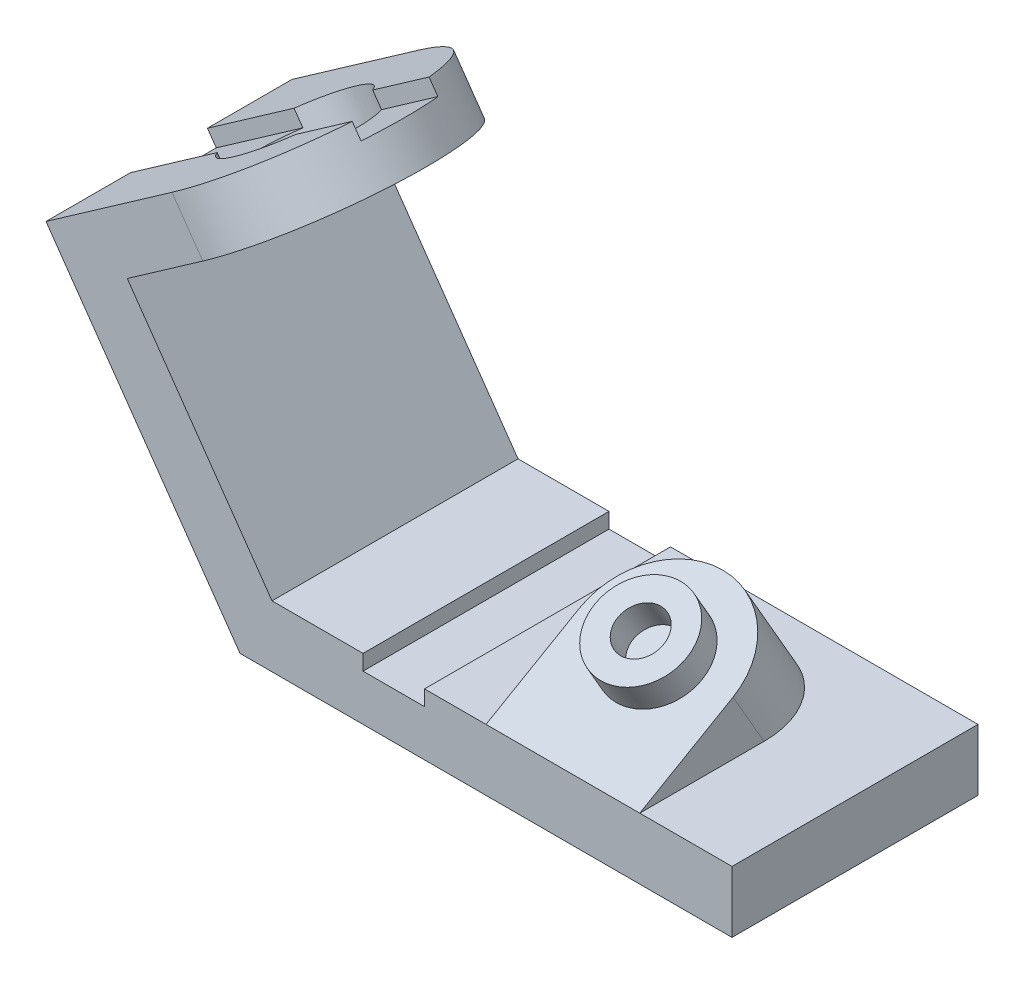
SolidWorks part; units mm, degrees
material "AISI 1020"
ref_plane "Front Plane" through (0, 0, 0) normal (0, 0, 1) x (1, 0, 0)
ref_plane "Top Plane" through (0, 0, 0) normal (0, 1, 0) x (1, 0, 0)
ref_plane "Right Plane" through (0, 0, 0) normal (1, 0, 0) x (0, 0, -1)
sketch "Sketch1" plane through (0, 0, 0) normal (0, 0, 1) x (1, 0, 0)
  line L0 (0, 0) -> (-203.2, 0)
  line L1 (0, 0) -> (0, 25.4)
  line L2 (0, 25.4) -> (-203.2, 25.4)
  line L3 (-203.2, 25.4) -> (-203.2, 0)
  dimension "D1" = 203.2
  dimension "D2" = 25.4
extrude "Boss-Extrude1" add sketch "Sketch1" against normal blind 101.6
sketch "Sketch2" plane through (0, 0, 0) normal (0, 0, 1) x (1, 0, 0)
  line L8 (0, 25.4) -> (-127, 25.4)
  line L9 (0, 25.4) -> (-203.2, 25.4) construction
  line L10 (-127, 25.4) -> (-127, 19.05)
  line L11 (-127, 19.05) -> (-152.4, 19.05)
  line L12 (-152.4, 19.05) -> (-152.4, 25.4)
  line L13 (-152.4, 25.4) -> (-127, 25.4)
  line M9 (0, 25.4) -> (-203.2, 25.4)
  dimension "D1" = 127
  dimension "D2" = 25.4
  dimension "D3" = 6.35
extrude "Cut-Extrude1" cut sketch "Sketch2" against normal through all contours L12 L11 L10 M9 region at (-139.7, 22.225, 0)
ref_axis "Axis1" through (10.16, 25.4, 0) along (-1, 0, 0)
ref_plane "Plane1" through (0, 19.05, 10.9985) normal (0, 0.866, 0.5) x (-1, 0, 0)
sketch "Sketch3" plane through (0, 19.05, 10.9985) normal (0, 0.866, 0.5) x (-1, 0, 0)
  line L0 (0, -12.7) -> (38.1, -12.7)
  line L1 (38.1, -12.7) -> (38.1, -57.15)
  line L2 (101.6, -57.15) -> (101.6, -12.7)
  line L3 (101.6, -12.7) -> (38.1, -12.7)
  line L4 (0, -100.6882) -> (127, -100.6882)
  line L5 (127, -100.6882) -> (127, -12.7)
  line L6 (127, -12.7) -> (0, -12.7)
  line L7 (0, -12.7) -> (0, -100.6882)
  line L8 (0, -100.6882) -> (127, -100.6882)
  line L9 (127, -100.6882) -> (127, -12.7)
  line L10 (127, -12.7) -> (0, -12.7)
  line L11 (0, -12.7) -> (0, -100.6882)
  arc A0 (38.1, -57.15) -> (101.6, -57.15) centre (69.85, -57.15) ccw
  dimension "D3" = 31.75
  dimension "D2" = 38.1
  dimension "D4" = 44.45
  dimension "D1" = 0
extrude "Boss-Extrude2" add sketch "Sketch3" against normal up to next contours L1 A0 L2 L3 region at (-69.85, 42.9275, -30.3586)
sketch "Sketch4" plane through (0, 19.05, 10.9985) normal (0, 0.866, 0.5) x (1, 0, 0)
  circle A0 centre (-69.85, 57.15) radius 19.05
  circle A1 centre (-69.85, 57.15) radius 9.525
  dimension "D1" = 38.1
  dimension "D2" = 19.05
extrude "Boss-Extrude3" add sketch "Sketch4" along normal blind 12.7
sketch "Sketch5" plane through (0, 0, 0) normal (0, 0, 1) x (1, 0, 0)
  line L0 (-203.2, 0) -> (-283.3286, 114.4355)
  line L3 (-203.2, 0) -> (0, 0) construction
  line L9 (-283.3286, 114.4355) -> (-262.5222, 129.0044)
  line L10 (-262.5222, 129.0044) -> (-182.3935, 14.5688)
  line L11 (-182.3935, 14.5688) -> (-203.2, 0)
  dimension "D1" = 55
  dimension "D2" = 139.7
  dimension "D3" = 25.4
extrude "Boss-Extrude4" add sketch "Sketch5" against normal blind 101.6
sketch "Sketch6" plane through (-146.9794, 209.9083, 0) normal (-0.5736, 0.8192, 0) x (0.8192, 0.5736, 0)
  line L0 (-166.4517, 0) -> (-102.9517, 0)
  line L1 (-166.4517, 101.6) -> (-102.9517, 101.6)
  line L3 (-166.4517, 101.6) -> (-166.4517, 0)
  arc A0 (-102.9517, 101.6) -> (-102.9517, 0) centre (-102.9517, 50.8) cw
  dimension "D1" = 63.5
extrude "Boss-Extrude5" add sketch "Sketch6" against normal blind 22.225
sketch "Sketch7" plane through (-146.9794, 209.9083, 0) normal (-0.5736, 0.8192, 0) x (0.8192, 0.5736, 0)
  circle A0 centre (-102.9517, 50.8) radius 12.7
  circle A1 centre (-102.9517, 50.8) radius 25.4
  dimension "D1" = 50.8
  dimension "D2" = 25.4
extrude "Cut-Extrude4" cut sketch "Sketch7" against normal blind 12.7
sketch "Sketch8" plane through (-146.9794, 209.9083, 0) normal (-0.5736, 0.8192, 0) x (0.8192, 0.5736, 0)
  circle A0 centre (-102.9517, 50.8) radius 12.7
  dimension "D1" = 25.4
extrude "Cut-Extrude5" cut sketch "Sketch8" against normal up to next
sketch "Sketch9" plane through (-146.9794, 209.9083, 0) normal (-0.5736, 0.8192, 0) x (0.8192, 0.5736, 0)
  line L0 (-166.4517, 101.6) -> (-166.4517, 66.675)
  line L1 (-166.4517, 101.6) -> (-166.4517, 0) construction
  line L2 (-49.7873, 66.675) -> (-166.4517, 66.675)
  line L3 (-166.4517, 0) -> (-166.4517, 34.925)
  line L4 (-166.4517, 66.675) -> (-166.4517, 34.925)
  line L5 (-166.4517, 34.925) -> (-49.7873, 34.925)
  line L6 (-49.7873, 34.925) -> (-49.7873, 66.675)
  circle M4 centre (-102.9517, 50.8) radius 25.4
  arc M6 (-102.9517, 0) -> (-102.9517, 101.6) centre (-102.9517, 50.8) ccw
  line M8 (-166.4517, 101.6) -> (-166.4517, 0)
  dimension "D1" = 34.925
  dimension "D2" = 34.925
extrude "Cut-Extrude6" cut sketch "Sketch9" against normal blind 6.35 contours L5 L2 M4 M6 | L5 L2 M8 M4 region at (-201.2029, 171.9406, -50.8) region at (-266.9726, 125.8881, -50.8)
